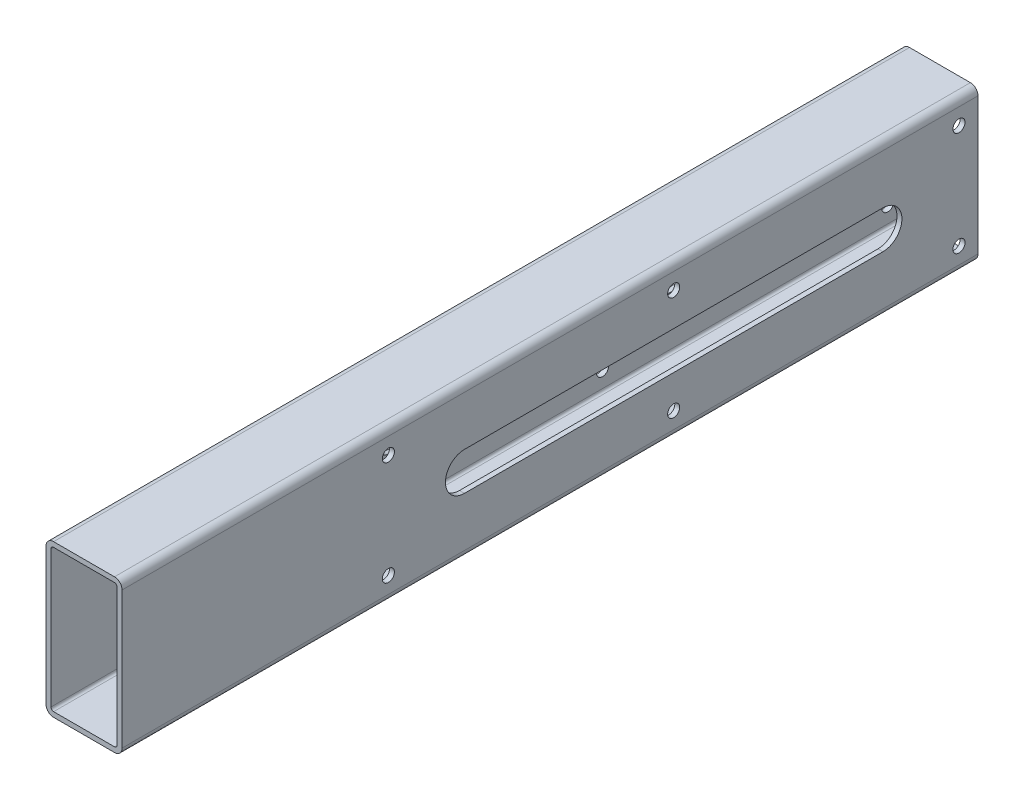
SolidWorks part; units mm, degrees
material "6061-T6 (SS)"
ref_plane "Front Plane" through (0, 0, 0) normal (0, 0, 1) x (1, 0, 0)
ref_plane "Top Plane" through (0, 0, 0) normal (0, 1, 0) x (1, 0, 0)
ref_plane "Right Plane" through (0, 0, 0) normal (1, 0, 0) x (0, 0, -1)
sketch "Sketch1" plane through (0, 0, 0) normal (0, 0, 1) x (1, 0, 0)
  line L1 (10.16, -25.4) -> (-10.16, -25.4)
  line L2 (12.7, -22.86) -> (12.7, 22.86)
  line L3 (10.16, 25.4) -> (-10.16, 25.4)
  line L4 (-12.7, -22.86) -> (-12.7, 22.86)
  line L5 (12.7, -25.4) -> (-12.7, 25.4) construction
  line L6 (12.7, 25.4) -> (-12.7, -25.4) construction
  arc A0 (-10.16, -25.4) -> (-12.7, -22.86) centre (-10.16, -22.86) cw
  arc A1 (10.16, -25.4) -> (12.7, -22.86) centre (10.16, -22.86) ccw
  arc A2 (12.7, 22.86) -> (10.16, 25.4) centre (10.16, 22.86) ccw
  arc A3 (-10.16, 25.4) -> (-12.7, 22.86) centre (-10.16, 22.86) ccw
  point P0 (0, 0)
  dimension "D3" = 2.54
  dimension "D1" = 25.4
  dimension "D2" = 50.8
extrude "Extrude-Thin1" add sketch "Sketch1" along normal blind 285.75 thin thin type one direction reverse wall 1.651
sketch "Sketch2" plane through (-12.7, 0, 0) normal (-1, 0, 0) x (0, 0, 1)
  line L0 (31.75, 0) -> (171.45, 0) construction
  line L1 (31.75, 6.35) -> (171.45, 6.35)
  line L2 (31.75, -6.35) -> (171.45, -6.35)
  line L3 (0, 22.86) -> (0, -22.86) construction
  arc A0 (31.75, 6.35) -> (31.75, -6.35) centre (31.75, 0) ccw
  arc A1 (171.45, -6.35) -> (171.45, 6.35) centre (171.45, 0) ccw
  point P3 (101.6, 0)
  dimension "D1" = 12.7
  dimension "D2" = 139.7
  dimension "D3" = 31.75
extrude "Cut-Extrude1" cut sketch "Sketch2" against normal through all
sketch "Sketch3" [suppressed] plane through (-12.7, 0, 0) normal (-1, 0, 0) x (0, 0, 1)
  line L0 (571.5, 0) -> (444.5, 0) construction
  line L1 (571.5, -6.35) -> (444.5, -6.35)
  line L2 (571.5, 6.35) -> (444.5, 6.35)
  line L3 (736.6, 22.86) -> (736.6, -22.86) construction
  arc A0 (571.5, -6.35) -> (571.5, 6.35) centre (571.5, 0) ccw
  arc A1 (444.5, 6.35) -> (444.5, -6.35) centre (444.5, 0) ccw
  point P3 (508, 0)
  dimension "D1" = 12.7
  dimension "D2" = 165.1
  dimension "D3" = 127
extrude "Cut-Extrude2" [suppressed] cut sketch "Sketch3" against normal through all
sketch "Sketch4" plane through (12.7, 0, 0) normal (1, 0, 0) x (0, 0, -1)
  circle A0 centre (-196.85, 17.399) radius 2.0193 construction
  circle A1 centre (-196.85, -17.399) radius 2.0193 construction
  circle A2 centre (-101.6, 17.399) radius 2.0193 construction
  circle A3 centre (-101.6, -17.399) radius 2.0193 construction
  circle A4 centre (-6.35, 17.399) radius 2.0193 construction
  circle A5 centre (-6.35, -17.399) radius 2.0193 construction
  circle A6 centre (-196.85, 17.399) radius 2.0193
  circle A7 centre (-196.85, -17.399) radius 2.0193
  circle A8 centre (-101.6, 17.399) radius 2.0193
  circle A9 centre (-101.6, -17.399) radius 2.0193
  circle A10 centre (-6.35, 17.399) radius 2.0193
  circle A11 centre (-6.35, -17.399) radius 2.0193
extrude "Cut-Extrude3" cut sketch "Sketch4" against normal through all
